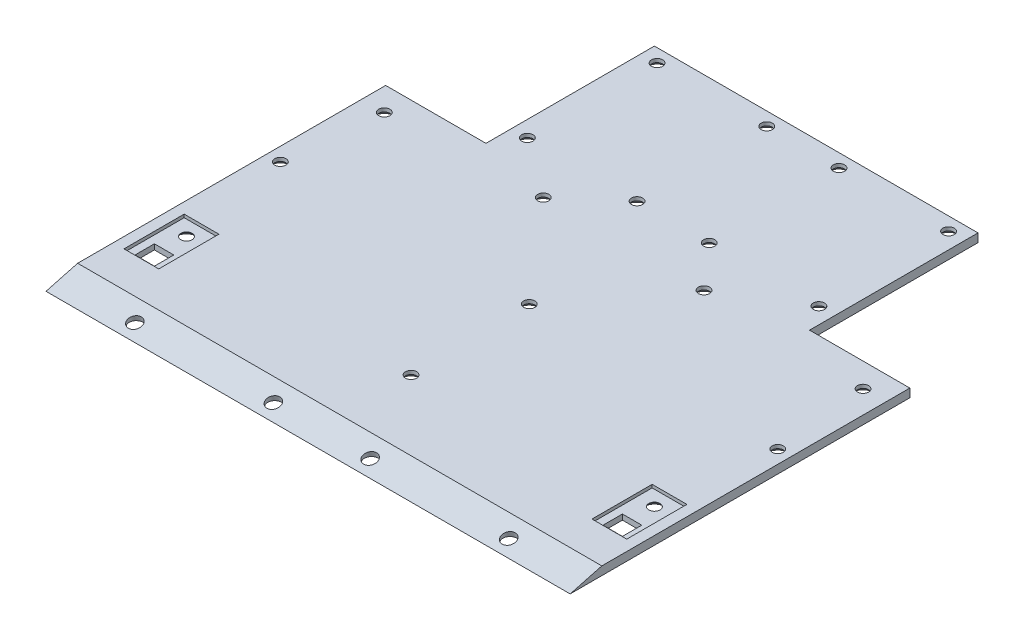
SolidWorks part; units mm, degrees
ref_plane "Alzado" through (0, 0, 0) normal (0, 0, 1) x (1, 0, 0)
ref_plane "Planta" through (0, 0, 0) normal (0, 1, 0) x (1, 0, 0)
ref_plane "Vista lateral" through (0, 0, 0) normal (1, 0, 0) x (0, 0, -1)
sketch "Croquis1" plane through (0, 0, 0) normal (1, 0, 0) x (0, 0, -1)
  line L0 (0, 0) -> (190, 0)
  line L1 (190, 0) -> (190, 3.17)
  line L2 (190, 3.17) -> (11.8306, 3.17)
  line L3 (0, 0) -> (11.8306, 3.17)
  dimension "D1" = 190
  dimension "D2" = 3.17
  dimension "D3" = 165
extrude "Saliente-Extruir1" add sketch "Croquis1" along normal blind 196
sketch "Croquis2" plane through (0, 0, 0) normal (0, -1, 0) x (-1, 0, 0)
  line L0 (0, 190) -> (0, 11.8306) construction
  line L1 (0, 127.0101) -> (-37.5, 127.0101)
  line L2 (0, 127.0101) -> (0, 190)
  line L3 (0, 190) -> (-37.5, 190)
  line L4 (-37.5, 127.0101) -> (-37.5, 190)
  line L5 (0, 127.0101) -> (-37.5, 190) construction
  line L6 (0, 190) -> (-37.5, 127.0101) construction
  line L7 (-196, 127.0101) -> (0, 127.0101) construction
  line L8 (-196, 190) -> (0, 190) construction
  line L9 (-37.5, 131.5) -> (-37.5, 190) construction
  point P4 (-18.75, 158.5051)
extrude "Cortar-Extruir1" cut sketch "Croquis2" against normal up to next
ref_plane "Plano1" through (98, 0, 0) normal (-1, 0, 0) x (0, 0, 1)
mirror "Simetría1" about plane through (98, 0, 0) normal (-1, 0, 0) of "Cortar-Extruir1"
sketch "Croquis3" plane through (0, 3.17, 0) normal (0, 1, 0) x (1, 0, 0)
  line L0 (196, 0) -> (0, 0) construction
  line L1 (4, 47.66) -> (17, 47.66)
  line L2 (4, 47.66) -> (4, 25.16)
  line L3 (4, 25.16) -> (17, 25.16)
  line L4 (17, 47.66) -> (17, 25.16)
  line L5 (4, 47.66) -> (17, 25.16) construction
  line L6 (4, 25.16) -> (17, 47.66) construction
  line L7 (0, 127.0101) -> (0, 11.8306) construction
  point P4 (10.5, 36.41)
  dimension "D1" = 25.16
  dimension "D2" = 22.5
  dimension "D3" = 13
  dimension "D4" = 4
extrude "Cortar-Extruir2" cut sketch "Croquis3" against normal blind 1.17
sketch "Croquis4" plane through (0, 2, 0) normal (0, 1, 0) x (1, 0, 0)
  line L0 (10.5, 25.16) -> (10.5, 26.41) construction
  line L1 (4, 25.16) -> (17, 25.16) construction
  line L2 (4, 26.41) -> (17, 26.41) construction
  line L3 (4, 47.66) -> (4, 25.16) construction
  line L4 (17, 25.16) -> (17, 47.66) construction
  line L5 (10.5, 26.41) -> (10.5, 33.66) construction
  line L6 (10.5, 30.035) -> (6.875, 30.035) construction
  line L7 (10.5, 30.035) -> (14.125, 30.035) construction
  line L8 (6.875, 30.035) -> (6.875, 26.41) construction
  line L9 (14.125, 30.035) -> (14.125, 33.66) construction
  dimension "D1" = 1.25
  dimension "D2" = 7.25
  dimension "D3" = 3.625
  dimension "D4" = 3.625
sketch "Croquis5" plane through (0, 2, 0) normal (0, 1, 0) x (1, 0, 0)
  line L1 (6.875, 26.41) -> (14.125, 26.41)
  line L2 (6.875, 26.41) -> (6.875, 33.66)
  line L3 (6.875, 33.66) -> (14.125, 33.66)
  line L4 (14.125, 26.41) -> (14.125, 33.66)
  line L5 (6.875, 26.41) -> (14.125, 33.66) construction
  line L6 (6.875, 33.66) -> (14.125, 26.41) construction
  point P4 (10.5, 30.035)
extrude "Cortar-Extruir3" cut sketch "Croquis5" against normal up to next
sketch "Croquis6" plane through (0, 2, 0) normal (0, 1, 0) x (1, 0, 0)
  line L0 (10.5, 47.66) -> (10.5, 46.41) construction
  line L1 (17, 47.66) -> (4, 47.66) construction
  line L2 (10.5, 46.41) -> (17, 46.41) construction
  line L3 (17, 25.16) -> (17, 47.66) construction
  line L4 (17, 46.41) -> (4, 46.41) construction
  line L5 (4, 47.66) -> (4, 25.16) construction
  circle A0 centre (10.5, 42.01) radius 1.6
  dimension "D2" = 3.2
  dimension "D1" = 1.25
  dimension "D3" = 4.4
extrude "Cortar-Extruir4" cut sketch "Croquis6" against normal up to next
mirror "Simetría2" about plane through (98, 0, 0) normal (-1, 0, 0) of "Cortar-Extruir2", "Cortar-Extruir4", "Cortar-Extruir3"
sketch "Sketch1" plane through (0, 3.17, 0) normal (0, 1, 0) x (1, 0, 0)
  circle A0 centre (8.5, 118.0101) radius 1.585
  circle A1 centre (187.5, 118.0101) radius 1.585
extrude "Cut-Extrude1" cut sketch "Sketch1" against normal up to next
sketch "Sketch2" plane through (0, 3.17, 0) normal (0, 1, 0) x (1, 0, 0)
  circle A0 centre (98.5, 38.0101) radius 1.585
extrude "Cut-Extrude2" cut sketch "Sketch2" against normal up to next
sketch "Sketch3" plane through (0, 3.17, 0) normal (0, 1, 0) x (1, 0, 0)
  circle A0 centre (43.5, 185) radius 1.5799
  circle A1 centre (84.5, 185) radius 1.585
  circle A2 centre (152.5, 185) radius 1.585
  circle A3 centre (111.5, 185) radius 1.585
  circle A4 centre (111.5, 136.5) radius 1.585
  circle A5 centre (152.5, 136.5) radius 1.585
  circle A6 centre (84.5, 136.5) radius 1.585
  circle A7 centre (43.5, 136.5) radius 1.585
extrude "Cut-Extrude3" cut sketch "Sketch3" against normal up to next
sketch "Sketch4" plane through (0, 3.17, 0) normal (0, 1, 0) x (1, 0, 0)
  circle A0 centre (65.7764, 120.1669) radius 1.6
  circle A1 centre (125.8764, 120.1669) radius 1.6
extrude "Cut-Extrude4" cut sketch "Sketch4" against normal blind 4.9
hole_wizard "Avellanado para tornillo con cabeza avellanada en cruz de M3.51" positions "3DSketch1" profile "Sketch5" countersink size "M3.5" standard "AS"
sketch3d "3DSketch1"
  line L0 (187.5, 0, -118.0101) -> (187.5, 3.17, -118.0101) construction
  line L1 (152.5, 0, -136.5) -> (152.5, 3.17, -136.5) construction
  line L2 (125.8764, 0, -120.1669) -> (125.8764, 3.17, -120.1669) construction
  line L3 (111.5, 0, -136.5) -> (111.5, 3.17, -136.5) construction
  line L4 (84.5, 0, -136.5) -> (84.5, 3.17, -136.5) construction
  line L5 (65.7764, 0, -120.1669) -> (65.7764, 3.17, -120.1669) construction
  line L6 (43.5, 0, -136.5) -> (43.5, 3.17, -136.5) construction
  line L7 (8.5, 0, -118.0101) -> (8.5, 3.17, -118.0101) construction
  line L8 (43.5, 0, -185) -> (43.5, 3.17, -185) construction
  line L9 (84.5, 0, -185) -> (84.5, 3.17, -185) construction
  line L10 (111.5, 0, -185) -> (111.5, 3.17, -185) construction
  line L11 (152.5, 0, -185) -> (152.5, 3.17, -185) construction
  line L12 (10.5, 0, -42.01) -> (10.5, 2, -42.01) construction
  line L13 (98.5, 0, -38.0101) -> (98.5, 3.17, -38.0101) construction
  line L14 (185.5, 0, -42.01) -> (185.5, 2, -42.01) construction
  point P0 (187.5, 0, -118.0101)
  point P4 (152.5, 0, -136.5)
  point P8 (125.8764, 0, -120.1669)
  point P12 (111.5, 0, -136.5)
  point P16 (84.5, 0, -136.5)
  point P20 (65.7764, 0, -120.1669)
  point P24 (43.5, 0, -136.5)
  point P28 (8.5, 0, -118.0101)
  point P32 (43.5, 0, -185)
  point P36 (84.5, 0, -185)
  point P40 (111.5, 0, -185)
  point P44 (152.5, 0, -185)
  point P48 (10.5, 0, -42.01)
  point P52 (98.5, 0, -38.0101)
  point P56 (185.5, 0, -42.01)
sketch "Sketch5" plane through (187.5, 0, -118.0101) normal (1, 0, 0) x (0, 0, -1)
  line L0 (0, 0) -> (0, 11.2618)
  line L1 (0, 11.2618) -> (2.1, 10)
  line L2 (2.1, 10) -> (2.1, 1.8348)
  line L3 (2.1, 1.8348) -> (4, 0)
  line L5 (4, 0) -> (0, 0)
  line L6 (-2.1, 1.8348) -> (-4, 0) construction
  line L10 (0, 11.2618) -> (-2.1, 10) construction
  line L11 (0, -6.35) -> (0, 107.95) construction
  dimension "Diámetro de taladro" = 4.2
  dimension "Profundidad de taladro" = 10
  dimension "Ángulo de avellanado cercano" = 8
  dimension "Ángulo de avellanado lejano" = 92
  dimension "Ángulo de perforador" = 118
sketch "Sketch6" plane through (0, 3.17, 0) normal (0, 1, 0) x (1, 0, 0)
  circle A0 centre (191.0671, 82.5578) radius 1.585
  circle A1 centre (97.6819, 83.0385) radius 1.585
  circle A2 centre (5.0671, 82.5578) radius 1.585
extrude "Cut-Extrude5" cut sketch "Sketch6" against normal blind 10
sketch "Sketch8" plane through (0, 0, 0) normal (0, 0.9659, 0.2588) x (1, 0, 0)
  circle A0 centre (28.1, 5.3001) radius 2.5
  circle A1 centre (79.9, 5.3001) radius 2.5
  circle A2 centre (116.1, 5.3001) radius 2.5
  circle A3 centre (167.9, 5.3001) radius 2.5
extrude "Cut-Extrude6" cut sketch "Sketch8" against normal blind 10
hole_wizard "Avellanado para tornillo con cabeza avellanada en cruz de M3.53" positions "3DSketch3" profile "Sketch10" countersink size "M3.5" standard "AS"
sketch3d "3DSketch3"
  line L0 (97.6819, 0, -83.0385) -> (97.6819, 3.17, -83.0385) construction
  line L1 (5.0671, 0, -82.5578) -> (5.0671, 3.17, -82.5578) construction
  line L2 (191.0671, 0, -82.5578) -> (191.0671, 3.17, -82.5578) construction
  point P0 (97.6819, 0, -83.0385)
  point P4 (5.0671, 0, -82.5578)
  point P8 (191.0671, 0, -82.5578)
sketch "Sketch10" plane through (97.6819, 0, -83.0385) normal (1, 0, 0) x (0, 0, -1)
  line L0 (0, 0) -> (0, 11.2618)
  line L1 (0, 11.2618) -> (2.1, 10)
  line L2 (2.1, 10) -> (2.1, 1.8348)
  line L3 (2.1, 1.8348) -> (4, 0)
  line L5 (4, 0) -> (0, 0)
  line L6 (-2.1, 1.8348) -> (-4, 0) construction
  line L10 (0, 11.2618) -> (-2.1, 10) construction
  line L11 (0, -6.35) -> (0, 107.95) construction
  dimension "Diámetro de taladro" = 4.2
  dimension "Profundidad de taladro" = 10
  dimension "Ángulo de avellanado cercano" = 8
  dimension "Ángulo de avellanado lejano" = 92
  dimension "Ángulo de perforador" = 118
